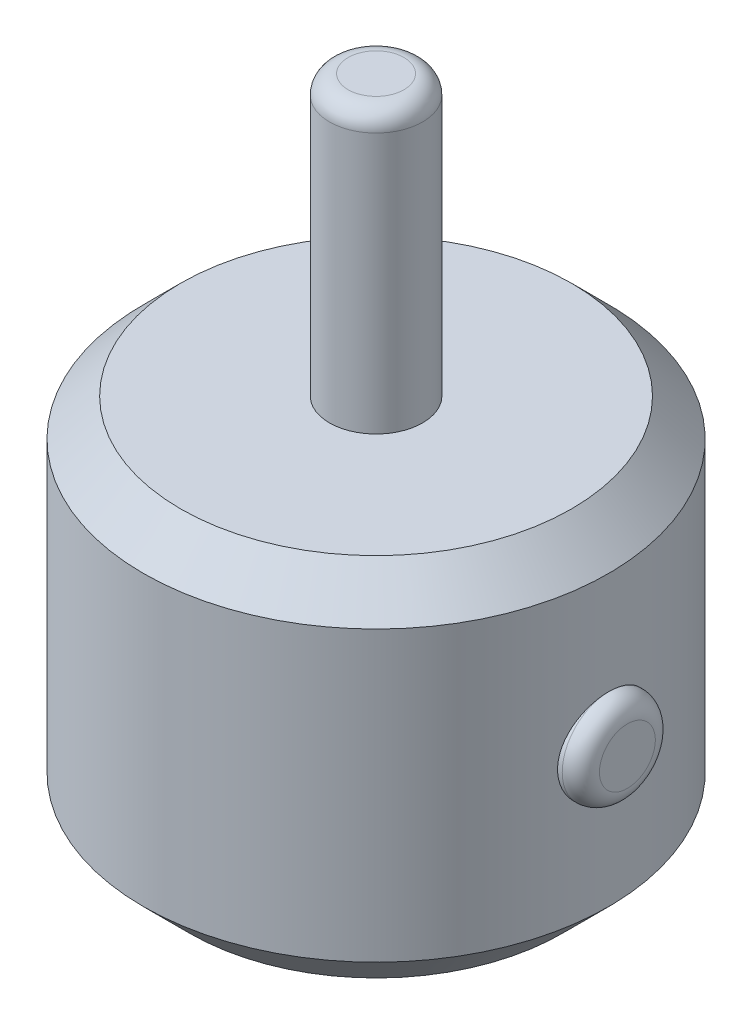
SolidWorks part; units mm, degrees
material "Aleación 1060"
ref_plane "Alzado" through (0, 0, 0) normal (0, 0, 1) x (1, 0, 0)
ref_plane "Planta" through (0, 0, 0) normal (0, 1, 0) x (1, 0, 0)
ref_plane "Vista lateral" through (0, 0, 0) normal (1, 0, 0) x (0, 0, -1)
sketch "Croquis1" plane through (0, 0, 0) normal (0, 1, 0) x (1, 0, 0)
  circle A0 centre (0, 0) radius 25
  dimension "D1" = 50
extrude "Saliente-Extruir1" add sketch "Croquis1" along normal blind 40
sketch "Croquis2" plane through (0, 40, 0) normal (0, 1, 0) x (1, 0, 0)
  circle A0 centre (0, 0) radius 5
  dimension "D1" = 10
extrude "Saliente-Extruir2" add sketch "Croquis2" along normal blind 30
fillet "Redondeo1" radius 2 1 edges at (0, 70, 5)
chamfer "Chaflán1" distance 4 angle 45 1 edges at (0, 40, 25)
ref_plane "Plano1" through (25, 0, 0) normal (-1, 0, 0) x (0, 0, 1)
sketch "Croquis3" plane through (25, 0, 0) normal (-1, 0, 0) x (0, 0, 1)
  line L0 (0, 0) -> (0, 40) construction
  line L1 (21, 40) -> (-21, 40) construction
  circle A0 centre (0, 20) radius 5
  dimension "D1" = 10
extrude "Saliente-Extruir3" add sketch "Croquis3" along normal blind 2 and the other way blind 2
fillet "Redondeo3" radius 2 1 edges at (27, 20, 5)
chamfer "Chaflán2" distance 5 angle 45 1 edges at (0, 0, 25)
